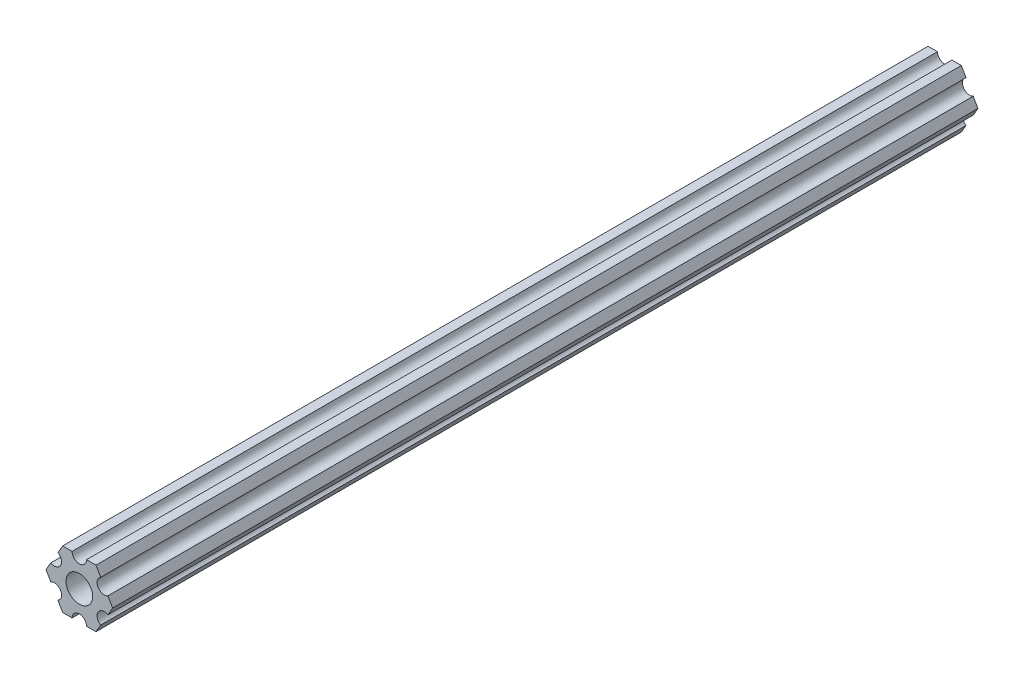
SolidWorks part; units mm, degrees
ref_plane "Front Plane" through (0, 0, 0) normal (0, 0, 1) x (1, 0, 0)
ref_plane "Top Plane" through (0, 0, 0) normal (0, 1, 0) x (1, 0, 0)
ref_plane "Right Plane" through (0, 0, 0) normal (1, 0, 0) x (0, 0, -1)
ref_plane "Plane1" through (0, 0, 0) normal (0, 0, -1) x (-1, 0, 0)
sketch "Sketch1" plane through (0, 0, 0) normal (0, 0, -1) x (-1, 0, 0)
  line L0 (-4.7055, -4.5498) -> (-3.6662, -6.35)
  line L1 (-3.6662, -6.35) -> (-1.5875, -6.35)
  line L2 (1.5875, -6.35) -> (3.6662, -6.35)
  line L3 (3.6662, -6.35) -> (4.7055, -4.5498)
  line L4 (6.293, -1.8002) -> (7.3323, 0)
  line L5 (7.3323, 0) -> (6.293, 1.8002)
  line L6 (4.7055, 4.5498) -> (3.6662, 6.35)
  line L7 (3.6662, 6.35) -> (1.5875, 6.35)
  line L8 (-1.5875, 6.35) -> (-3.6662, 6.35)
  line L9 (-3.6662, 6.35) -> (-4.7055, 4.5498)
  line L10 (-6.293, 1.8002) -> (-7.3323, 0)
  line L11 (-7.3323, 0) -> (-6.293, -1.8002)
  circle A0 centre (0, 0) radius 2.9337
  arc A1 (-6.293, -1.8002) -> (-4.7055, -4.5498) centre (-5.4993, -3.175) cw
  arc A2 (-1.5875, -6.35) -> (1.5875, -6.35) centre (0, -6.35) cw
  arc A3 (4.7055, -4.5498) -> (6.293, -1.8002) centre (5.4993, -3.175) cw
  arc A4 (6.293, 1.8002) -> (4.7055, 4.5498) centre (5.4993, 3.175) cw
  arc A5 (1.5875, 6.35) -> (-1.5875, 6.35) centre (0, 6.35) cw
  arc A6 (-4.7055, 4.5498) -> (-6.293, 1.8002) centre (-5.4993, 3.175) cw
extrude "Boss-Extrude1" add sketch "Sketch1" along normal blind 190.5
